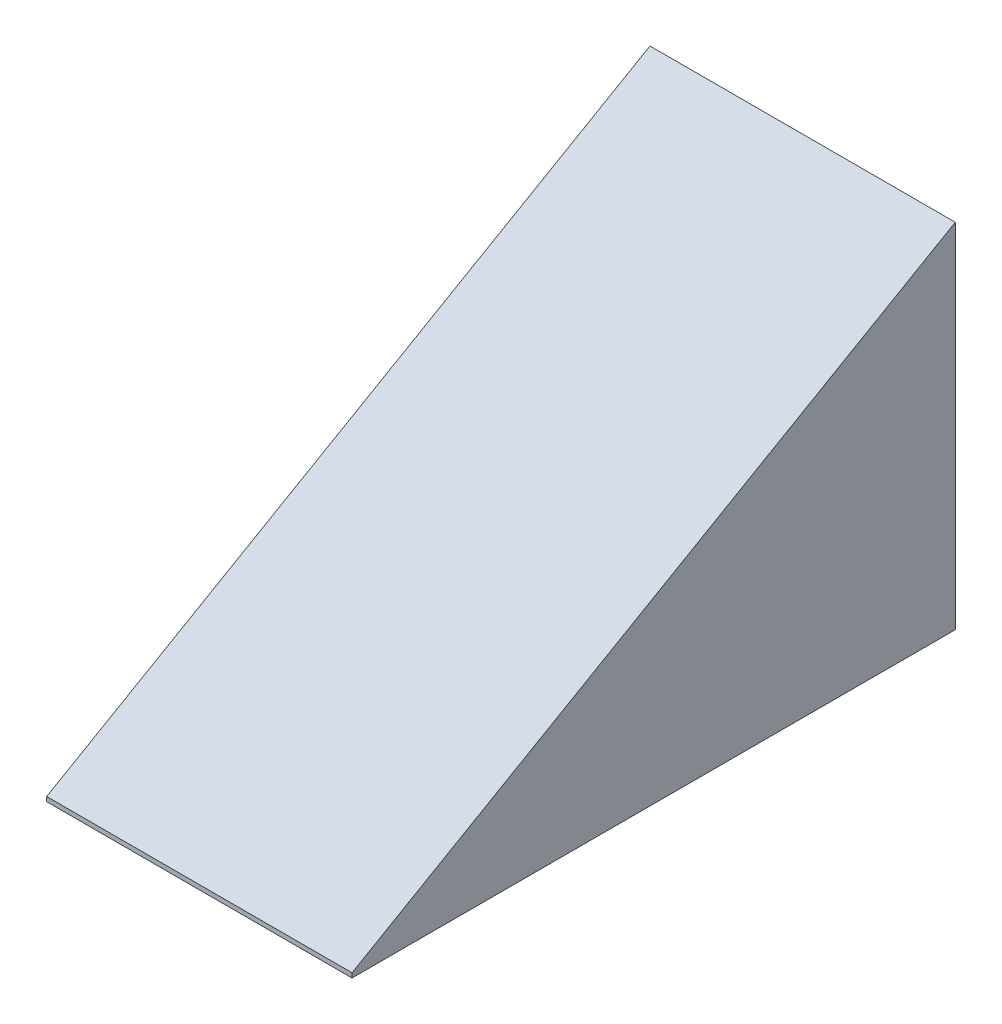
SolidWorks part; units mm, degrees
ref_plane "Front Plane"
ref_plane "Top Plane" through (0, 0, 0) normal (0, 1, 0) x (1, 0, 0)
ref_plane "Right Plane" through (0, 0, 0) normal (1, 0, 0) x (0, 0, -1)
sketch "Sketch1" plane through (0, 0, 0) normal (0, 0, 1) x (1, 0, 0)
  line L1 (-44.45, 99.06) -> (44.45, 99.06)
  line L2 (-44.45, 99.06) -> (-44.45, -53.34)
  line L3 (-44.45, -53.34) -> (44.45, -53.34)
  line L4 (44.45, 99.06) -> (44.45, -53.34)
  line L5 (-44.45, 99.06) -> (44.45, -53.34) construction
  line L6 (-44.45, -53.34) -> (44.45, 99.06) construction
  point P0 (0, 22.86)
  dimension "D1" = 88.9
  dimension "D2" = 152.4
  dimension "D3" = 22.86
extrude "Boss-Extrude1" add sketch "Sketch1" along normal blind 406.4
shell "Shell1" thickness 3.175 removed face at (0, 22.86, 0) removed face at (0, 22.86, 406.4) outward yes
sketch "Sketch2" plane through (0, 0, 0) normal (1, 0, 0) x (0, 0, -1)
  line L0 (0, -56.515) -> (0, 102.235) construction
  line L2 (0, 49.53) -> (0, -49.53)
  line L3 (0, -49.53) -> (-169.3772, -49.53)
  line L4 (-169.3772, -48.26) -> (-169.3772, -49.53)
  line L5 (-169.3772, -48.26) -> (0, 49.53)
  line L6 (-169.3772, -48.26) -> (-171.577, -49.53) construction
  line L7 (-171.577, -49.53) -> (-169.3772, -49.53) construction
  point P6 (0, 0)
  dimension "D1" = 1.27
  dimension "D2" = 30
  dimension "D3" = 99.06
extrude "Boss-Extrude2" add sketch "Sketch2" along normal mid plane 85.725 separate body
delete or keep bodies "Body-Delete/Keep 1" type delete bodies bodies 101
ref_point "Point2"
sketch "Sketch3" plane through (0, 0, 0) normal (0, 0, -1) x (-1, 0, 0)
  circle A0 centre (0, 0) radius 4.4323
  dimension "D1" = 8.8646
extrude "Cut-Extrude1" [suppressed] cut sketch "Sketch3" against normal blind 10.16 draft 8
